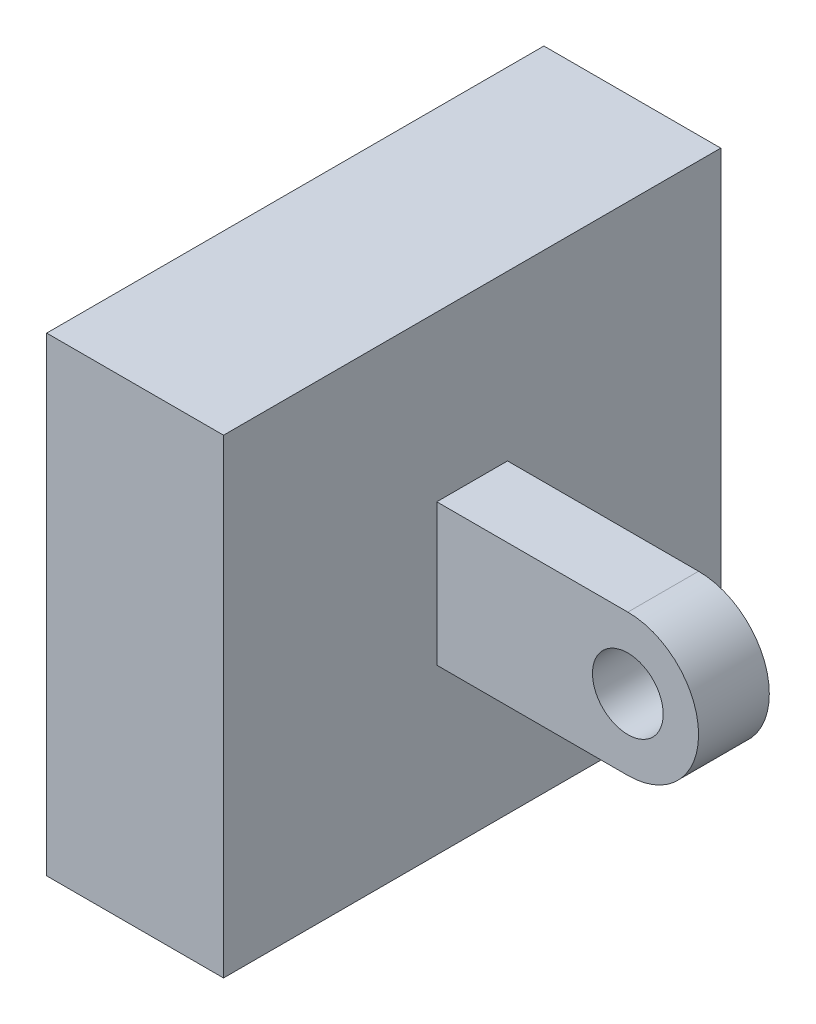
SolidWorks part; units mm, degrees
ref_plane "前视基准面" through (0, 0, 0) normal (0, 0, 1) x (1, 0, 0)
ref_plane "上视基准面" through (0, 0, 0) normal (0, 1, 0) x (1, 0, 0)
ref_plane "右视基准面" through (0, 0, 0) normal (1, 0, 0) x (0, 0, -1)
sketch "草图1" plane through (0, 0, 0) normal (0, 0, 1) x (1, 0, 0)
  line L0 (0, 40) -> (-108.0263, 40)
  line L1 (0, -40) -> (-108.0263, -40)
  line L2 (-108.0263, -40) -> (-108.0263, 40)
  arc A0 (0, 40) -> (0, -40) centre (0, 0) cw
  circle A1 centre (0, 0) radius 20
  dimension "D1" = 40
  dimension "D2" = 40
extrude "凸台-拉伸1" add sketch "草图1" along normal blind 20 and the other way blind 20
sketch "草图2" plane through (-108.0263, 0, 0) normal (-1, 0, 0) x (0, 0, 1)
  line L1 (-140.5759, -132.9038) -> (140.5759, -132.9038)
  line L2 (-140.5759, -132.9038) -> (-140.5759, 132.9038)
  line L3 (-140.5759, 132.9038) -> (140.5759, 132.9038)
  line L4 (140.5759, -132.9038) -> (140.5759, 132.9038)
  line L5 (-140.5759, -132.9038) -> (140.5759, 132.9038) construction
  line L6 (-140.5759, 132.9038) -> (140.5759, -132.9038) construction
extrude "凸台-拉伸2" add sketch "草图2" along normal blind 100
sketch "草图3" plane through (-208.0263, 0, 0) normal (-1, 0, 0) x (0, 0, 1)
  circle A0 centre (0, 0) radius 20
  dimension "D1" = 40
extrude "切除-拉伸1" cut sketch "草图3" against normal blind 20
